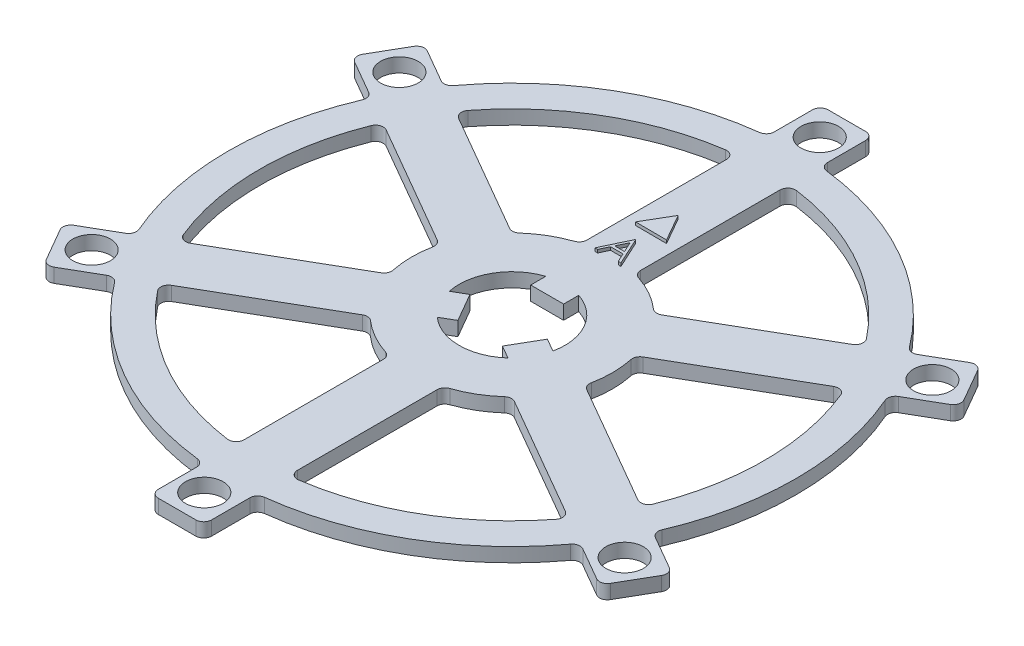
SolidWorks part; units mm, degrees
ref_plane "Front Plane" through (0, 0, 0) normal (0, 0, 1) x (1, 0, 0)
ref_plane "Top Plane" through (0, 0, 0) normal (0, 1, 0) x (1, 0, 0)
ref_plane "Right Plane" through (0, 0, 0) normal (1, 0, 0) x (0, 0, -1)
sketch "Sketch1" plane through (0, 0, 0) normal (0, 1, 0) x (1, 0, 0)
  line L0 (0, 35.3782) -> (0, -23.9127) construction
  line L1 (-12.8, 0) -> (12.8, 0) construction
  line L35 (3.2924, 36.0599) -> (3.2924, 42.8205)
  line L60 (6.6062, -1.3857) -> (4.938, -0.4225)
  line L62 (-2.1031, 6.414) -> (-2.1031, 4.4877)
  line L63 (-2.1031, 4.4877) -> (2.0969, 4.4877)
  line L64 (2.0969, 6.416) -> (2.0969, 4.4877)
  line L68 (4.508, -5.024) -> (2.838, -4.0598)
  line L69 (4.938, -0.4225) -> (2.838, -4.0598)
  line L70 (-4.5031, -5.0283) -> (-2.8349, -4.0652)
  line L72 (-6.6049, -1.3921) -> (-4.9349, -0.4279)
  line L73 (-2.8349, -4.0652) -> (-4.9349, -0.4279)
  line L74 (0, 39.2598) -> (-34, 19.6299) construction
  line L75 (-34, 19.6299) -> (-34, -19.6299) construction
  line L76 (-34, -19.6299) -> (0, -39.2598) construction
  line L77 (0, -39.2598) -> (34, -19.6299) construction
  line L78 (34, -19.6299) -> (34, 19.6299) construction
  line L79 (34, 19.6299) -> (0, 39.2598) construction
  line L81 (3.2924, 12.3693) -> (3.2924, 32.0218)
  line L82 (3.2924, 42.8205) -> (-3.4879, 42.8205)
  line L83 (-3.4879, 12.3156) -> (-3.4879, 32.0011)
  line L84 (0, 22.0676) -> (-3.4879, 42.8205) construction
  line L85 (3.2924, 42.8205) -> (0, 22.0676) construction
  line L86 (-3.4879, 36.0415) -> (-3.4879, 42.8205)
  line L87 (8.9217, 9.1784) -> (25.9698, 19.0211)
  line L88 (12.3584, 3.3333) -> (29.3779, 13.1596)
  line L89 (32.875, 15.1786) -> (38.7299, 18.5589)
  line L90 (29.4689, 21.0413) -> (35.3397, 24.4309)
  line L91 (38.7299, 18.5589) -> (35.3397, 24.4309)
  line L92 (12.4096, -3.1372) -> (29.4577, -12.9799)
  line L93 (9.0659, -9.036) -> (26.0855, -18.8622)
  line L94 (29.5825, -20.8812) -> (35.4374, -24.2616)
  line L95 (32.9568, -15.0001) -> (38.8276, -18.3897)
  line L96 (35.4374, -24.2616) -> (38.8276, -18.3897)
  line L97 (3.4879, -12.3156) -> (3.4879, -32.0011)
  line L98 (-3.2924, -12.3693) -> (-3.2924, -32.0218)
  line L99 (-3.2924, -36.0599) -> (-3.2924, -42.8205)
  line L100 (3.4879, -36.0415) -> (3.4879, -42.8205)
  line L101 (-3.2924, -42.8205) -> (3.4879, -42.8205)
  line L102 (-8.9217, -9.1784) -> (-25.9698, -19.0211)
  line L103 (-12.3584, -3.3333) -> (-29.3779, -13.1596)
  line L104 (-32.875, -15.1786) -> (-38.7299, -18.5589)
  line L105 (-29.4689, -21.0413) -> (-35.3397, -24.4309)
  line L106 (-38.7299, -18.5589) -> (-35.3397, -24.4309)
  line L107 (-12.4096, 3.1372) -> (-29.4577, 12.9799)
  line L108 (-9.0659, 9.036) -> (-26.0855, 18.8622)
  line L109 (-29.5825, 20.8812) -> (-35.4374, 24.2616)
  line L110 (-32.9568, 15.0001) -> (-38.8276, 18.3897)
  line L111 (-35.4374, 24.2616) -> (-38.8276, 18.3897)
  arc A0 (-3.4879, 12.3156) -> (-9.0659, 9.036) centre (0, 0) ccw
  arc A5 (-2.1031, 6.414) -> (-6.6049, -1.3921) centre (0, 0) ccw
  arc A6 (-4.5031, -5.0283) -> (4.508, -5.024) centre (0, 0) ccw
  arc A7 (6.6062, -1.3857) -> (2.0969, 6.416) centre (0, 0) ccw
  circle A8 centre (0, 0) radius 34 construction
  circle A9 centre (0, 39.2598) radius 2.4
  arc A10 (-29.4577, 12.9799) -> (-29.3779, -13.1596) centre (0, 0) ccw
  arc A11 (-3.4879, 36.0415) -> (-29.5825, 20.8812) centre (0, 0) ccw
  circle A12 centre (34, 19.6299) radius 2.4
  circle A13 centre (34, -19.6299) radius 2.4
  circle A14 centre (0, -39.2598) radius 2.4
  circle A15 centre (-34, -19.6299) radius 2.4
  circle A16 centre (-34, 19.6299) radius 2.4
  arc A17 (-12.4096, 3.1372) -> (-12.3584, -3.3333) centre (0, 0) ccw
  arc A18 (-8.9217, -9.1784) -> (-3.2924, -12.3693) centre (0, 0) ccw
  arc A19 (3.4879, -12.3156) -> (9.0659, -9.036) centre (0, 0) ccw
  arc A20 (12.4096, -3.1372) -> (12.3584, 3.3333) centre (0, 0) ccw
  arc A21 (8.9217, 9.1784) -> (3.2924, 12.3693) centre (0, 0) ccw
  arc A22 (-25.9698, -19.0211) -> (-3.2924, -32.0218) centre (0, 0) ccw
  arc A23 (3.4879, -32.0011) -> (26.0855, -18.8622) centre (0, 0) ccw
  arc A24 (29.4577, -12.9799) -> (29.3779, 13.1596) centre (0, 0) ccw
  arc A25 (25.9698, 19.0211) -> (3.2924, 32.0218) centre (0, 0) ccw
  arc A26 (-3.4879, 32.0011) -> (-26.0855, 18.8622) centre (0, 0) ccw
  arc A27 (-32.9568, 15.0001) -> (-32.875, -15.1786) centre (0, 0) ccw
  arc A28 (-29.4689, -21.0413) -> (-3.2924, -36.0599) centre (0, 0) ccw
  arc A29 (3.4879, -36.0415) -> (29.5825, -20.8812) centre (0, 0) ccw
  arc A30 (32.9568, -15.0001) -> (32.875, 15.1786) centre (0, 0) ccw
  arc A31 (29.4689, 21.0413) -> (3.2924, 36.0599) centre (0, 0) ccw
  point P3 (0, 9.9)
  point P8 (0, 22.0676)
  point P11 (0, 6.1614)
  point P26 (0, 0)
  point P40 (0, 0)
  point P42 (0, 0)
  point P43 (0, 0)
  point P44 (0, 0)
  point P98 (0, 0)
  dimension "D1" = 68
  dimension "D6" = 3
  dimension "D5" = 4.2
  dimension "D2" = 6
extrude "Boss-Extrude1" add sketch "Sketch1" along normal blind 1.8
ref_plane "Plane1" through (0, 1.2, 0) normal (0, 1, 0) x (1, 0, 0)
sketch "Sketch3" plane through (0, 1.2, 0) normal (0, 1, 0) x (1, 0, 0)
  line L0 (0, 0) -> (0, 34.3448) construction
  line L1 (-3.4879, 14.3853) -> (3.2924, 14.3853) construction
  line L5 (0, 21.2972) -> (-1.4698, 18.7514)
  line L6 (-1.4698, 18.7514) -> (1.4698, 18.7514)
  line L7 (1.4698, 18.7514) -> (0, 21.2972)
  line L8 (-3.4879, 12.3156) -> (-3.4879, 32.0011) construction
  line L9 (3.2924, 32.0218) -> (3.2924, 12.3693) construction
  circle A0 centre (0, 19.6) radius 0.8486 construction
  text T0 "A\r\n"
extrude "Boss-Extrude2" add sketch "Sketch3" along normal blind 0.4
fillet "Fillet1" radius 1 48 edges at (29.4689, 0.9, -21.0413) (3.2924, 0.9, -32.0218) (25.9698, 0.9, -19.0211) (29.3779, 0.9, -13.1596) (29.4577, 0.9, 12.9799) (35.3397, 0.9, -24.4309) (38.7299, 0.9, -18.5589) (32.875, 0.9, -15.1786) (38.8276, 0.9, 18.3897) (32.9568, 0.9, 15.0001) (12.3584, 0.9, -3.3333) (12.4096, 0.9, 3.1372) (26.0855, 0.9, 18.8622) (3.4879, 0.9, 32.0011) (35.4374, 0.9, 24.2616) (29.5825, 0.9, 20.8812) (9.0659, 0.9, 9.036) (3.4879, 0.9, 12.3156) (3.4879, 0.9, 36.0415) (3.4879, 0.9, 42.8205) (-3.2924, 0.9, 42.8205) (-3.2924, 0.9, 36.0599) (-3.2924, 0.9, 32.0218) (-8.9217, 0.9, 9.1784) (-3.2924, 0.9, 12.3693) (-25.9698, 0.9, 19.0211) (-29.4689, 0.9, 21.0413) (-35.3397, 0.9, 24.4309) (-38.7299, 0.9, 18.5589) (-32.875, 0.9, 15.1786) (-29.3779, 0.9, 13.1596) (-29.4577, 0.9, -12.9799) (-12.3584, 0.9, 3.3333) (-12.4096, 0.9, -3.1372) (-32.9568, 0.9, -15.0001) (-38.8276, 0.9, -18.3897) (8.9217, 0.9, -9.1784) (-35.4374, 0.9, -24.2616) (3.2924, 0.9, -36.0599) (3.2924, 0.9, -42.8205) (3.2924, 0.9, -12.3693) (-26.0855, 0.9, -18.8622) (-3.4879, 0.9, -36.0415) (-29.5825, 0.9, -20.8812) (-3.4879, 0.9, -12.3156) (-9.0659, 0.9, -9.036) (-3.4879, 0.9, -42.8205) (-3.4879, 0.9, -32.0011)
ref_plane "Plane2" through (0, 1.8, 0) normal (0, 1, 0) x (1, 0, 0)
sketch "Sketch4" plane through (0, 1.8, 0) normal (0, 1, 0) x (1, 0, 0)
  line L0 (0, 0) -> (0, 29.1505) construction
  line L1 (-3.0789, 12.2924) -> (2.9677, 12.2924) construction
  line L2 (0.011, 21.1866) -> (-1.9915, 17.7562)
  line L3 (-1.9915, 17.7562) -> (1.9805, 17.7373)
  line L4 (1.9805, 17.7373) -> (0.011, 21.1866)
  circle A0 centre (0, 18.8934) radius 1.1466 construction
  text T0 "A"
extrude "Boss-Extrude3" add sketch "Sketch4" along normal blind 0.4
scale "Scale1" bodies to scale 103 scale about centroid uniform scaling yes scale factor 1.15
